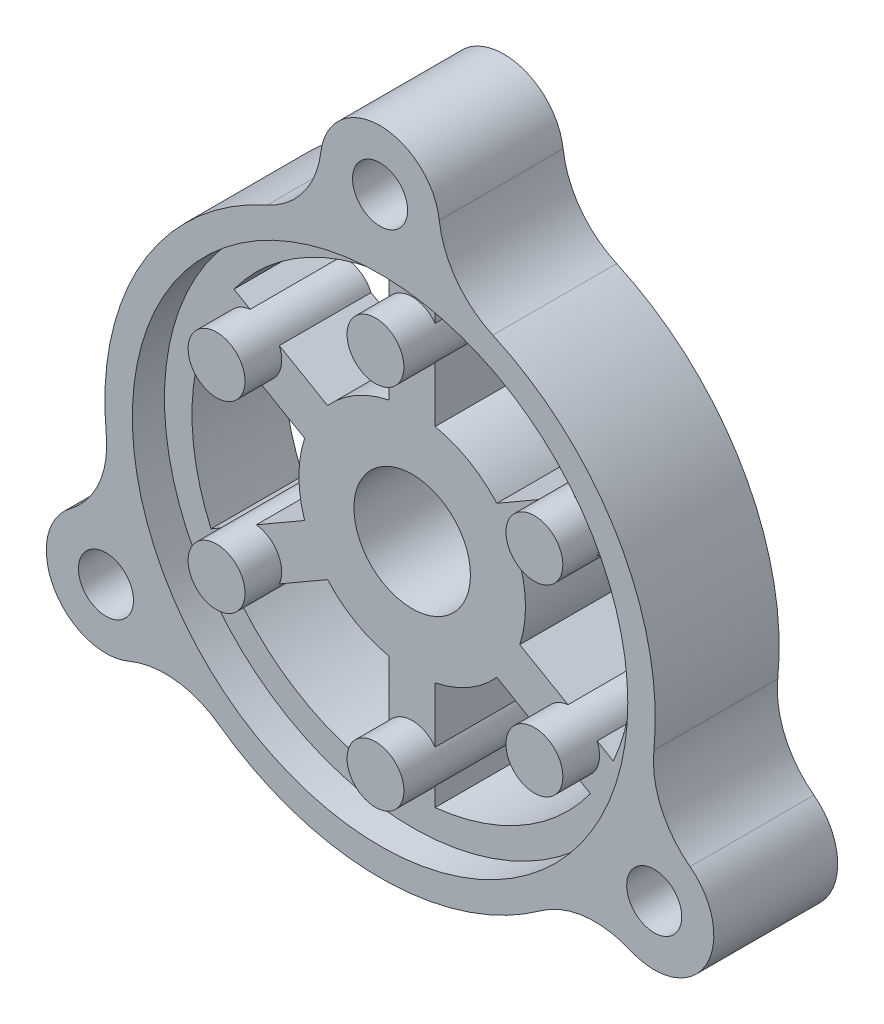
SolidWorks part; units mm, degrees
ref_plane "Front Plane" through (0, 0, 0) normal (0, 0, 1) x (1, 0, 0)
ref_plane "Top Plane" through (0, 0, 0) normal (0, 1, 0) x (1, 0, 0)
ref_plane "Right Plane" through (0, 0, 0) normal (1, 0, 0) x (0, 0, -1)
sketch "Sketch1" plane through (0, 0, 0) normal (0, 0, 1) x (1, 0, 0)
  circle A0 centre (0, 0) radius 15
  dimension "D1" = 30
extrude "Boss-Extrude1" add sketch "Sketch1" along normal blind 5
sketch "Sketch2" plane through (0, 0, 5) normal (0, 0, 1) x (1, 0, 0)
  circle A0 centre (0, 0) radius 12
  circle A1 centre (0, 0) radius 6.175
  circle A2 centre (0, 0) radius 3.175
  circle A3 centre (0, 0) radius 15 construction
  dimension "D1" = 6.35
  dimension "D2" = 3
  dimension "D3" = 3
extrude "Cut-Extrude1" cut sketch "Sketch2" against normal through all contours A2 | A0 A1 region at (-11.6606, 0, 5) region at (0, 0, 5)
sketch "Sketch4" plane through (0, 0, 0) normal (0, 0, 1) x (1, 0, 0)
  line L1 (0, 10) -> (-8.6603, 5) construction
  line L2 (-8.6603, 5) -> (-8.6603, -5) construction
  line L3 (-8.6603, -5) -> (0, -10) construction
  line L4 (0, -10) -> (8.6603, -5) construction
  line L5 (8.6603, -5) -> (8.6603, 5) construction
  line L6 (8.6603, 5) -> (0, 10) construction
  circle A0 centre (0, 0) radius 8.6603 construction
  circle A1 centre (0, 10) radius 1.55
  circle A2 centre (-8.6603, 5) radius 1.55
  circle A3 centre (-8.6603, -5) radius 1.55
  circle A4 centre (0, -10) radius 1.55
  circle A5 centre (8.6603, -5) radius 1.55
  circle A6 centre (8.6603, 5) radius 1.55
  dimension "D2" = 3.1
  dimension "D1" = 20
extrude "Boss-Extrude2" add sketch "Sketch4" along normal offset from surface (7 mm away) 2 up to face at (12, 0, 5) offset beyond the face yes
sketch "Sketch5" plane through (0, 0, 0) normal (0, 0, -1) x (-1, 0, 0)
  line L1 (1.25, 14.9478) -> (-1.25, 14.9478)
  line L2 (1.25, 14.9478) -> (1.25, 6.0472)
  line L3 (1.25, 6.0472) -> (-1.25, 6.0472)
  line L4 (-1.25, 14.9478) -> (-1.25, 6.0472)
  circle A0 centre (0, 0) radius 15 construction
  circle A1 centre (0, 0) radius 6.175 construction
  dimension "D1" = 2.5
extrude "Boss-Extrude3" add sketch "Sketch5" against normal up to surface (5 mm away) up to face at (12, 0, 5)
ref_axis "Axis1" through (0, 0, 0) along (0, 0, 1)
pattern_circular "CirPattern1" count 6 every 60 about axis through (0, 0, 0) along (0, 0, 1) of "Boss-Extrude3"
sketch "Sketch6" plane through (0, 0, 5) normal (0, 0, 1) x (1, 0, 0)
  circle A0 centre (0, 0) radius 15
  circle A1 centre (0, 0) radius 13.5
  circle A2 centre (0, 0) radius 15 construction
  dimension "D1" = 27
extrude "Boss-Extrude4" add sketch "Sketch6" along normal blind 1.75
sketch "Sketch7" plane through (0, 0, 0) normal (0, 0, -1) x (-1, 0, 0)
  line L0 (0, 17.25) -> (0, 0) construction
  circle A0 centre (0, 17.25) radius 3.25
  circle A1 centre (0, 17.25) radius 1.5
  dimension "D1" = 3
  dimension "D2" = 6.5
  dimension "D3" = 17.25
extrude "Boss-Extrude5" add sketch "Sketch7" against normal up to surface (6.75 mm away) up to face at (15, 0, 6.75)
fillet "Fillet2" radius 5 2 edges at (2.1811, 14.8406, 3.375) (-2.1811, 14.8406, 3.375)
pattern_circular "CirPattern2" count 3 every 120 about axis through (0, 0, 0) along (0, 0, 1) of "Fillet2", "Boss-Extrude5"
